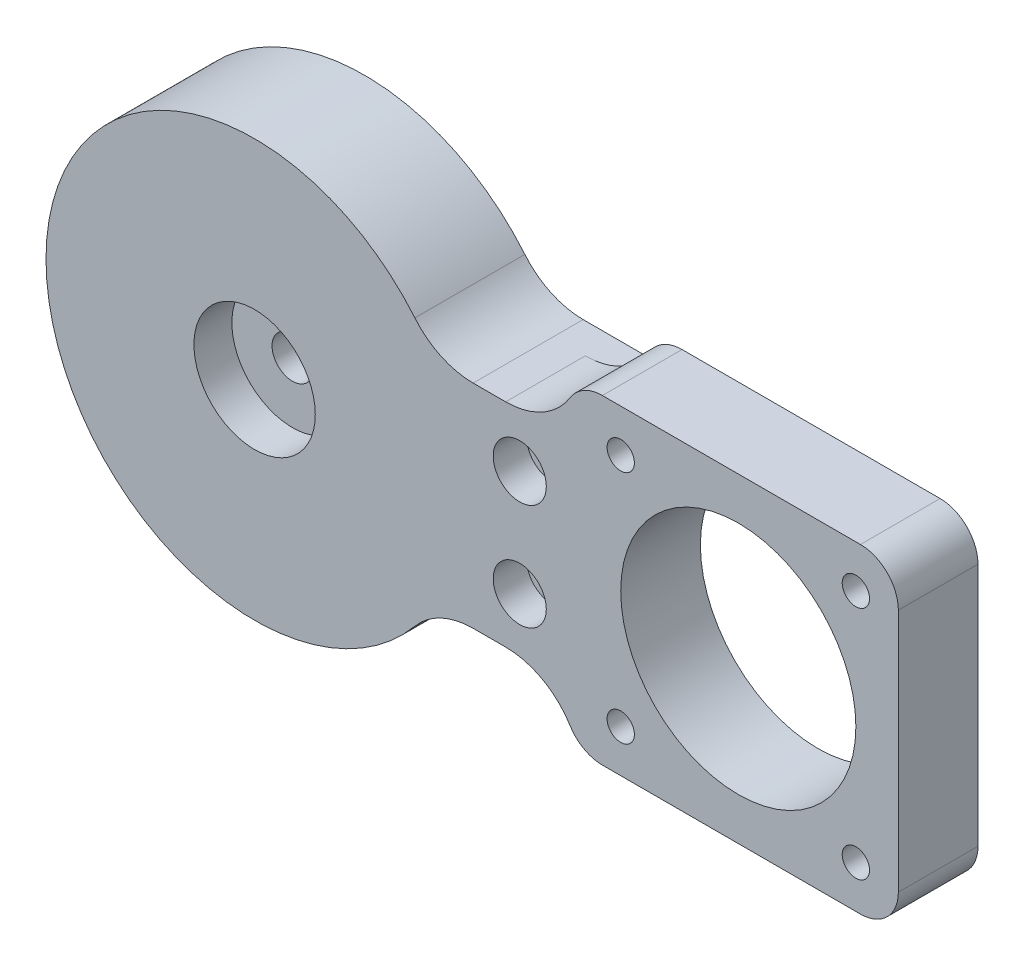
SolidWorks part; units mm, degrees
material "ABS"
ref_plane "Front Plane" through (0, 0, 0) normal (0, 0, 1) x (1, 0, 0)
ref_plane "Top Plane" through (0, 0, 0) normal (0, 1, 0) x (1, 0, 0)
ref_plane "Right Plane" through (0, 0, 0) normal (1, 0, 0) x (0, 0, -1)
sketch "Sketch1" plane through (0, 0, 0) normal (0, 0, 1) x (1, 0, 0)
  line L0 (42.6696, 14) -> (42.6696, 21.1)
  line L1 (23.6696, -14) -> (42.6696, -14)
  line L3 (23.6696, 14) -> (42.6696, 14)
  line L7 (42.6696, -21.1) -> (84.8696, -21.1)
  line L8 (42.6696, -21.1) -> (42.6696, -14)
  line L9 (42.6696, 21.1) -> (84.8696, 21.1)
  line L10 (84.8696, -21.1) -> (84.8696, 21.1)
  line L11 (42.6696, -21.1) -> (84.8696, 21.1) construction
  line L12 (42.6696, 21.1) -> (84.8696, -21.1) construction
  line L13 (48.2696, -15.5) -> (79.2696, -15.5) construction
  line L14 (48.2696, -15.5) -> (48.2696, 15.5) construction
  line L15 (48.2696, 15.5) -> (79.2696, 15.5) construction
  line L16 (79.2696, -15.5) -> (79.2696, 15.5) construction
  line L17 (48.2696, -15.5) -> (79.2696, 15.5) construction
  line L18 (48.2696, 15.5) -> (79.2696, -15.5) construction
  arc A0 (23.6696, 14) -> (23.6696, -14) centre (0, 0) ccw
  circle A2 centre (63.7696, 0) radius 15.5
  circle A3 centre (48.2696, 15.5) radius 1.5
  circle A4 centre (79.2696, 15.5) radius 1.5
  circle A5 centre (79.2696, -15.5) radius 1.5
  circle A6 centre (48.2696, -15.5) radius 1.5
  circle A7 centre (0, 0) radius 2.7
  point P3 (27.5, 0)
  point P8 (63.7696, 0)
  point P18 (63.7696, 0)
  dimension "D7" = 31
  dimension "D8" = 27.5
  dimension "D3" = 5.4
  dimension "D1" = 28
  dimension "D2" = 42.2
  dimension "D4" = 19
  dimension "D5" = 42.2
  dimension "D6" = 31
extrude "Boss-Extrude1" add sketch "Sketch1" along normal blind 14.5
ref_plane "Plane1" through (0, 0, 14.5) normal (0, 0, 1) x (1, 0, 0)
sketch "Sketch2" plane through (0, 0, 0) normal (0, 0, -1) x (-1, 0, 0)
  line L1 (-84.8696, -21.1) -> (-42.6696, -21.1)
  line L2 (-84.8696, -21.1) -> (-84.8696, 21.1)
  line L3 (-84.8696, 21.1) -> (-42.6696, 21.1)
  line L4 (-42.6696, -21.1) -> (-42.6696, 21.1)
  line L5 (-84.8696, -21.1) -> (-42.6696, 21.1) construction
  line L6 (-84.8696, 21.1) -> (-42.6696, -21.1) construction
  circle A0 centre (-63.7696, 0) radius 15.5 construction
  point P0 (-63.7696, 0)
extrude "Cut-Extrude1" cut sketch "Sketch2" against normal blind 4
sketch "Sketch3" plane through (0, 0, 14.5) normal (0, 0, 1) x (1, 0, 0)
  circle A0 centre (0, 0) radius 8
  dimension "D1" = 16
extrude "Cut-Extrude2" cut sketch "Sketch3" against normal blind 5
fillet "Fillet2" radius 10 4 edges at (42.6696, -14, 9.25) (42.6696, 14, 9.25) (23.6696, -14, 7.25) (23.6696, 14, 7.25)
sketch "Sketch5" plane through (0, 0, 14.5) normal (0, 0, 1) x (1, 0, 0)
  point P0 (79.2696, -15.5)
  point P3 (79.2696, 15.5)
  point P6 (48.2696, 15.5)
  point P9 (48.2696, -15.5)
hole_wizard "Taladro de margen para M31" positions "Sketch5" profile "Sketch6" hole size "M3" standard "Ansi Metric" end condition through all
sketch "Sketch6" plane through (79.2696, -15.5, 14.5) normal (1, 0, 0) x (0, -1, 0)
  line L0 (0, 0) -> (0, 14.5)
  line L1 (0, 14.5) -> (1.8, 14.5)
  line L2 (1.8, 14.5) -> (1.8, 0)
  line L5 (1.8, 0) -> (0, 0)
  line L11 (0, -6.35) -> (0, 107.95) construction
  dimension "Diámetro de taladro hasta el siguiente" = 3.6
  dimension "Profundidad de taladro hasta el siguiente" = 14.5
sketch "Sketch7" plane through (0, 0, 14.5) normal (0, 0, 1) x (1, 0, 0)
  line L0 (30.9567, 14) -> (30.9567, -14) construction
  line L1 (33.0993, 14) -> (28.8141, 14) construction
  line L2 (28.8141, -14) -> (33.0993, -14) construction
  line L3 (-969.0433, 0) -> (49030.9567, 0) construction
  line L4 (34.9567, -14) -> (34.9567, 14) construction
  circle A0 centre (34.9567, 7) radius 1.5
  circle A1 centre (34.9567, -7) radius 1.5
  point P11 (30.9567, 0)
  point P13 (0, 0)
  point P16 (0, 0)
  dimension "D2" = 3
  dimension "D1" = 7
  dimension "D3" = 7
  dimension "D4" = 4
extrude "Cut-Extrude3" cut sketch "Sketch7" against normal through all
sketch "Sketch8" plane through (0, 0, 14.5) normal (0, 0, 1) x (1, 0, 0)
  point P0 (34.9567, 7)
  point P3 (34.9567, -7)
hole_wizard "Refrentado para tornillo con cabeza troncocónica de M31" positions "Sketch8" profile "Sketch9" counterbore size "M3" standard "Ansi Metric" end condition through all
sketch "Sketch9" plane through (34.9567, 7, 14.5) normal (1, 0, 0) x (0, -1, 0)
  line L0 (0, 0) -> (0, 14.5)
  line L1 (0, 14.5) -> (1.8, 14.5)
  line L3 (1.8, 14.5) -> (1.8, 4.4)
  line L4 (1.8, 4.4) -> (3.5, 4.4)
  line L5 (3.5, 4.4) -> (3.5, 0)
  line L7 (3.5, 0) -> (0, 0)
  line L11 (0, -6.35) -> (0, 107.95) construction
  dimension "Diámetro de taladro hasta el siguiente" = 3.6
  dimension "Profundidad de taladro hasta el siguiente" = 14.5
  dimension "Diámetro de refrentado" = 7
  dimension "Profundidad de refrentado" = 4.4
fillet "Fillet3" radius 5 4 edges at (42.6696, -21.1, 9.25) (84.8696, -21.1, 9.25) (84.8696, 21.1, 9.25) (42.6696, 21.1, 9.25)
